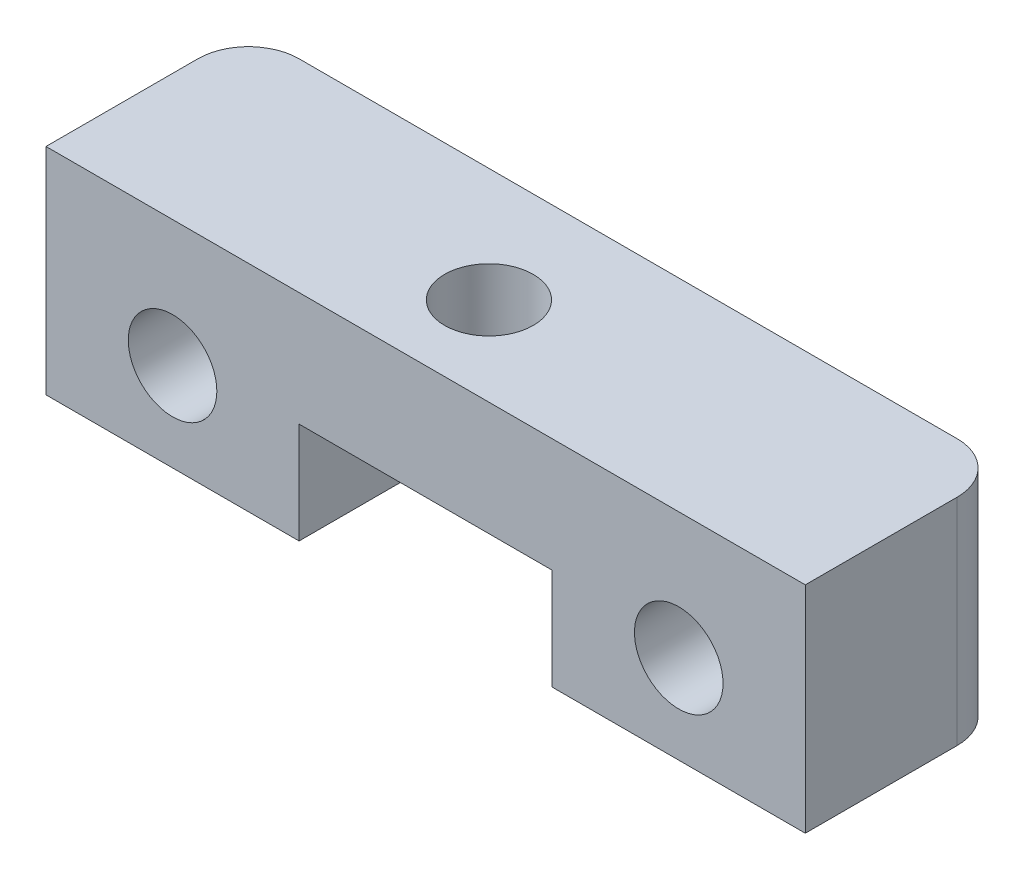
SolidWorks part; units mm, degrees
ref_plane "Front Plane" through (0, 0, 0) normal (0, 0, 1) x (1, 0, 0)
ref_plane "Top Plane" through (0, 0, 0) normal (0, 1, 0) x (1, 0, 0)
ref_plane "Right Plane" through (0, 0, 0) normal (1, 0, 0) x (0, 0, -1)
sketch "Sketch1" plane through (0, 0, 0) normal (0, 1, 0) x (1, 0, 0)
  line L0 (-1, -0.5) -> (-1, -4) construction
  line L5 (-15, 4) -> (15, 4)
  line L6 (-15, 4) -> (-15, -4)
  line L7 (-15, -4) -> (15, -4)
  line L8 (15, 4) -> (15, -4)
  line L9 (-15, 4) -> (15, -4) construction
  line L10 (-15, -4) -> (15, 4) construction
  line L11 (-1, 0) -> (0, 0) construction
  circle A0 centre (-1, -0.5) radius 1.75
  point P0 (0, 0)
  dimension "D3" = 3.5
  dimension "D1" = 30
  dimension "D2" = 8
  dimension "D4" = 3.5
  dimension "D5" = 1
extrude "Boss-Extrude1" add sketch "Sketch1" along normal blind 2
sketch "Sketch2" plane through (0, 0, 4) normal (0, 0, 1) x (1, 0, 0)
  line L0 (-10, -3) -> (10, -3) construction
  line L1 (-15, 0) -> (-5, 0)
  line L2 (-15, 0) -> (-15, -6.5)
  line L3 (-15, -6.5) -> (-5, -6.5)
  line L4 (-5, -2.5) -> (-5, -6.5)
  line L5 (15, 0) -> (5, 0)
  line L6 (15, 0) -> (15, -6.5)
  line L7 (15, -6.5) -> (5, -6.5)
  line L8 (5, -2.5) -> (5, -6.5)
  line L9 (-5, -2.5) -> (5, -2.5)
  line L10 (-15, 2) -> (15, 2) construction
  line L11 (-15, 0) -> (15, 0) construction
  line L23 (-5, 0) -> (5, 0)
  circle A2 centre (-10, -3) radius 1.75
  circle A3 centre (10, -3) radius 1.75
  point P12 (-10, 0)
  point P13 (10, 0)
  point P17 (0, -3)
  point P22 (0, 0)
  point P24 (0, -2.5)
  dimension "D1" = 3.5
  dimension "D2" = 3.5
  dimension "D3" = 5
  dimension "D4" = 6.5
  dimension "D5" = 20
  dimension "D6" = 4
  dimension "D7" = 10
extrude "Boss-Extrude2" add sketch "Sketch2" against normal up to surface (8 mm away) up to face at (0, 1, -4)
fillet "Fillet1" radius 2 2 edges at (-15, -2.25, -4) (15, -2.25, -4)
sketch "Sketch3" plane through (0, 0, 0) normal (0, 1, 0) x (1, 0, 0)
  circle A1 centre (-1, -0.5) radius 1.75
  circle A2 centre (-1, -0.5) radius 1.75
  dimension "D1" = 0
extrude "Cut-Extrude1" cut sketch "Sketch3" against normal through all
